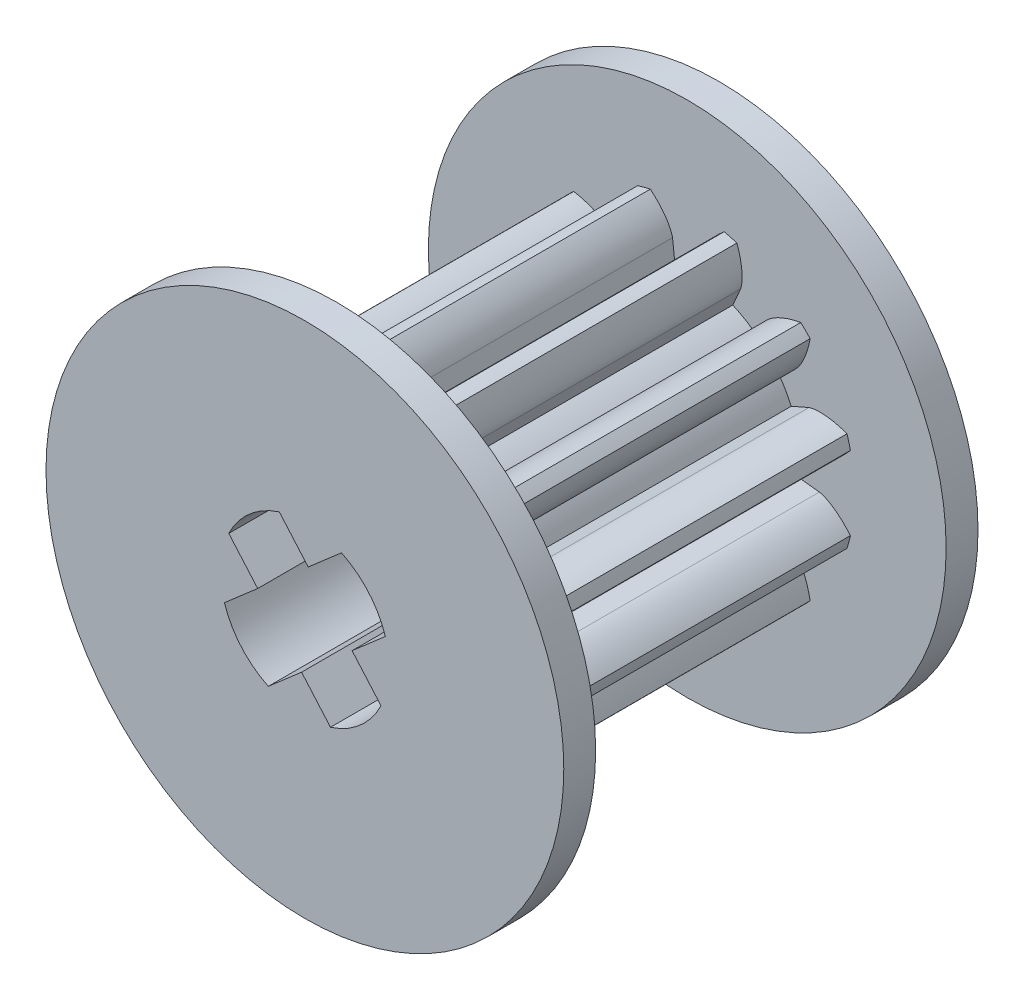
SolidWorks part; units mm, degrees
material "ABS"
ref_plane "Front Plane" through (0, 0, 0) normal (0, 0, 1) x (1, 0, 0)
ref_plane "Top Plane" through (0, 0, 0) normal (0, 1, 0) x (1, 0, 0)
ref_plane "Right Plane" through (0, 0, 0) normal (1, 0, 0) x (0, 0, -1)
ref_axis "Axis1" [suppressed] through (0, 0, 71.2135) along (0, 0, -1)
sketch "Sketch1" plane through (0, 0, 0) normal (0, 0, 1) x (1, 0, 0)
  circle A0 centre (0, 0) radius 3.5625
  circle A1 centre (0, 0) radius 4.1723
  circle A2 centre (0, 0) radius 3.75
  circle A3 centre (0, 0) radius 4.5
  circle A4 centre (0, 0) radius 5.25
  dimension "Pitch" = 9
  dimension "Addendum" = 10.5
  dimension "Clearance" = 7.5
  dimension "Base" = 8.3447
  dimension "Root" = 7.125
extrude "Boss-Extrude1" add sketch "Sketch1" along normal blind 11 contours A4
sketch "Sketch3" plane through (0, 0, 0) normal (0, 0, 1) x (1, 0, 0)
  line L0 (0.4615, 4.1467) -> (0, 0) construction
  line L1 (0.7855, 4.0977) -> (0, 0) construction
  line L2 (1.1046, 4.0235) -> (0, 0) construction
  line L3 (1.4168, 3.9244) -> (0, 0) construction
  line L4 (1.7204, 3.8011) -> (0, 0) construction
  line L5 (2.0133, 3.6544) -> (0, 0) construction
  line L6 (2.2938, 3.4852) -> (0, 0) construction
  line L7 (2.5602, 3.2945) -> (0, 0) construction
  line L8 (2.8108, 3.0835) -> (0, 0) construction
  line L9 (3.044, 2.8534) -> (0, 0) construction
  line L10 (3.2585, 2.6058) -> (0, 0) construction
  line L11 (0.7855, 4.0977) -> (0.4636, 4.1594) construction
  line L12 (3.2585, 2.6058) -> (1.2119, 5.1651) construction
  line L13 (1.1046, 4.0235) -> (0.4725, 4.197) construction
  line L14 (1.4168, 3.9244) -> (0.4922, 4.2582) construction
  line L15 (1.7204, 3.8011) -> (0.5262, 4.3416) construction
  line L16 (2.0133, 3.6544) -> (0.5782, 4.4451) construction
  line L17 (2.2938, 3.4852) -> (0.6514, 4.5662) construction
  line L18 (2.5602, 3.2945) -> (0.7489, 4.702) construction
  line L19 (2.8108, 3.0835) -> (0.8734, 4.8495) construction
  line L20 (3.044, 2.8534) -> (1.0271, 5.0051) construction
  line L21 (0, 0) -> (0, 4.5) construction
  line L22 (0, 0) -> (0.5874, 4.4615)
  line L23 (0, 0) -> (-0.5874, 4.4615)
  line L24 (0.4615, 4.1467) -> (0.3941, 3.5406)
  line L25 (-0.4615, 4.1467) -> (-0.3941, 3.5406)
  circle A0 centre (0, 0) radius 4.1723 construction
  circle A1 centre (0, 0) radius 4.5 construction
  arc A2 (3.2585, 2.6058) -> (0.4615, 4.1467) centre (0, 0) ccw construction
  circle A3 centre (0, 0) radius 3.5625 construction
  circle A4 centre (0, 0) radius 3.5625
  circle A5 centre (0, 0) radius 5.25 construction
  circle A6 centre (0, 0) radius 5.25
  spline S0 degree 3 poles (0.4615, 4.1467) (0.464, 4.1637) (0.473, 4.2013) (0.4941, 4.2666) (0.5286, 4.35) (0.6061, 4.5031) (0.722, 4.6743) (0.9298, 4.9199) (1.0915, 5.0686) (1.2119, 5.1651) knots 0 0 0 0 0.040008 0.090018 0.16003 0.250047 0.489907 0.639935 1 1 1 1
  spline S1 degree 3 poles (-0.4615, 4.1467) (-0.464, 4.1637) (-0.473, 4.2013) (-0.4941, 4.2666) (-0.5286, 4.35) (-0.6061, 4.5031) (-0.722, 4.6743) (-0.9298, 4.9199) (-1.0915, 5.0686) (-1.2119, 5.1651) knots 0 0 0 0 0.040008 0.090018 0.16003 0.250047 0.489907 0.639935 1 1 1 1
  point P18 (0, 0)
  dimension "D2" = 45
  dimension "D3" = 0.3277
  dimension "D4" = 3.2769
  dimension "D5" = 0.6554
  dimension "D6" = 0.9831
  dimension "D7" = 1.3108
  dimension "D8" = 1.6385
  dimension "D9" = 1.9662
  dimension "D10" = 2.2939
  dimension "D11" = 2.6216
  dimension "D12" = 2.9492
  dimension "D13" = 15
  dimension "D1" = 11
extrude "Cut-Extrude3" cut sketch "Sketch3" along normal through all contours S1 L25 A4 L24 S0 A6 region at (0, 4.5519, 0)
fillet "Fillet2" [suppressed] radius 0.05
pattern_circular "CirPattern1" count 12 over 360 about axis through (0, 0, 71.2135) along (0, 0, -1) of "Cut-Extrude3", "Fillet2"
ref_plane "Plane2" through (0, 0, 5.5) normal (0, 0, 1) x (1, 0, 0)
sketch "Sketch6" plane through (0, 0, 11) normal (0, 0, 1) x (1, 0, 0)
  circle A0 centre (0, 0) radius 8.125
  dimension "D1" = 16.25
extrude "Boss-Extrude2" add sketch "Sketch6" along normal blind 1
mirror "Mirror1" about plane through (0, 0, 5.5) normal (0, 0, 1) of "Boss-Extrude2"
sketch "Sketch5" plane through (0, 0, 0) normal (0, 0, 1) x (1, 0, 0)
  line L0 (-0.8803, 2.2327) -> (0.0791, 1.1286) construction
  line L1 (-1.1286, 0.0791) -> (-2.088, 1.1833) construction
  line L2 (-2.2327, -0.8803) -> (-1.1286, 0.0791) construction
  line L3 (-0.0791, -1.1286) -> (-1.1833, -2.088) construction
  line L4 (0.8803, -2.2327) -> (-0.0791, -1.1286) construction
  line L5 (1.1286, -0.0791) -> (2.088, -1.1833) construction
  line L6 (2.2327, 0.8803) -> (1.1286, -0.0791) construction
  line L7 (0.0791, 1.1286) -> (1.1833, 2.088) construction
  line L8 (-0.8803, 2.2327) -> (0.0791, 1.1286)
  line L9 (-1.1286, 0.0791) -> (-2.088, 1.1833)
  line L10 (-2.2327, -0.8803) -> (-1.1286, 0.0791)
  line L11 (-0.0791, -1.1286) -> (-1.1833, -2.088)
  line L12 (0.8803, -2.2327) -> (-0.0791, -1.1286)
  line L13 (1.1286, -0.0791) -> (2.088, -1.1833)
  line L14 (2.2327, 0.8803) -> (1.1286, -0.0791)
  line L15 (0.0791, 1.1286) -> (1.1833, 2.088)
  line L16 (0.1039, 1.4813) -> (1.1479, 2.3885)
  line L17 (-0.8033, 2.5253) -> (0.1039, 1.4813)
  line L18 (-1.4813, 0.1039) -> (-2.3885, 1.1479)
  line L19 (-2.5253, -0.8033) -> (-1.4813, 0.1039)
  line L20 (-0.1039, -1.4813) -> (-1.1479, -2.3885)
  line L21 (0.8033, -2.5253) -> (-0.1039, -1.4813)
  line L22 (1.4813, -0.1039) -> (2.3885, -1.1479)
  line L23 (2.5253, 0.8033) -> (1.4813, -0.1039)
  arc A0 (-0.8803, 2.2327) -> (-2.088, 1.1833) centre (0, 0) ccw construction
  arc A1 (-2.2327, -0.8803) -> (-1.1833, -2.088) centre (0, 0) ccw construction
  arc A2 (0.8803, -2.2327) -> (2.088, -1.1833) centre (0, 0) ccw construction
  arc A3 (2.2327, 0.8803) -> (1.1833, 2.088) centre (0, 0) ccw construction
  arc A4 (-0.8803, 2.2327) -> (-2.088, 1.1833) centre (0, 0) ccw
  arc A5 (-2.2327, -0.8803) -> (-1.1833, -2.088) centre (0, 0) ccw
  arc A6 (0.8803, -2.2327) -> (2.088, -1.1833) centre (0, 0) ccw
  arc A7 (2.2327, 0.8803) -> (1.1833, 2.088) centre (0, 0) ccw
  arc A10 (2.5253, 0.8033) -> (1.1479, 2.3885) centre (0, 0) ccw
  arc A11 (-0.8033, 2.5253) -> (-2.3885, 1.1479) centre (0, 0) ccw
  arc A13 (-2.5253, -0.8033) -> (-1.1479, -2.3885) centre (0, 0) ccw
  arc A14 (0.8033, -2.5253) -> (2.3885, -1.1479) centre (0, 0) ccw
  dimension "D1" = 0.25
extrude "Cut-Extrude4" cut sketch "Sketch5" along normal through all both and the other way through all contours L14 A7 L15 L8 A4 L9 L10 A5 L11 L12 A6 L13 | L21 A14 L22 L23 A10 L16 L17 A11 L18 L19 A13 L20 A7 L14 L13 A6 L12 L11 A5 L10 L9 A4 L8 L15 region at (0, 0, 0) region at (0.6727, 1.881, 0)
equation "\"Module\"= .75"
equation "\"numTeeth\"= 12"
equation "\"pressureAngle\"= 22deg"
equation "\"toothRadius\"= .05"
equation "\"Pitch@Sketch1\"=\"Module\"*\"numTeeth\""
equation "\"Addendum@Sketch1\"=\"Pitch@Sketch1\"+\"Module\"*2"
equation "\"Clearance@Sketch1\"=\"Pitch@Sketch1\"-\"Module\"*2"
equation "\"Base@Sketch1\"=\"Pitch@Sketch1\"*cos(\"pressureAngle\")"
equation "\"Root@Sketch1\"=\"Pitch@Sketch1\"-\"Module\"*1.25*2"
equation "\"D4@Sketch3\"= \"Base@Sketch1\" * pi / 8"
equation "\"D3@Sketch3\"= \"D4@Sketch3\" / 10"
equation "\"D5@Sketch3\"=\"D3@Sketch3\"*2"
equation "\"D6@Sketch3\"=\"D3@Sketch3\"*3"
equation "\"D7@Sketch3\"=\"D3@Sketch3\"*4"
equation "\"D8@Sketch3\"=\"D3@Sketch3\"*5"
equation "\"D9@Sketch3\"=\"D3@Sketch3\"*6"
equation "\"D10@Sketch3\"=\"D3@Sketch3\"*7"
equation "\"D11@Sketch3\"=\"D3@Sketch3\"*8"
equation "\"D12@Sketch3\"=\"D3@Sketch3\"*9"
equation "\"D13@Sketch3\"=180/\"numTeeth\""
equation "\"D1@CirPattern1\"=\"numTeeth\""
equation "\"D1@Fillet2\"= \"toothRadius\""
